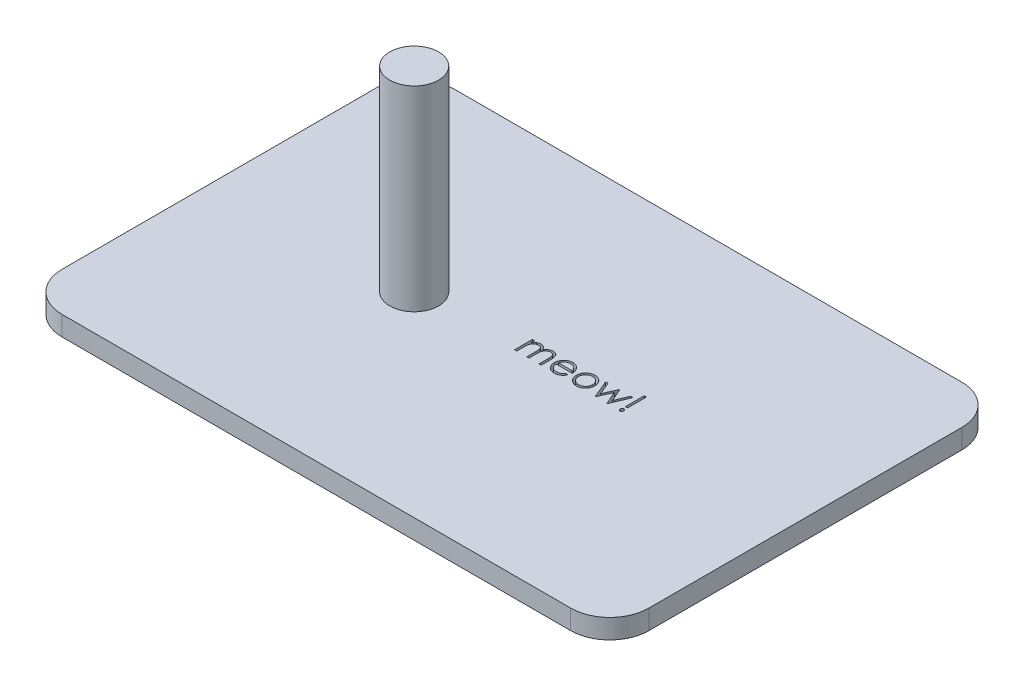
SolidWorks part; units mm, degrees
ref_plane "Front Plane" through (0, 0, 0) normal (0, 0, 1) x (1, 0, 0)
ref_plane "Top Plane" through (0, 0, 0) normal (0, 1, 0) x (1, 0, 0)
ref_plane "Right Plane" through (0, 0, 0) normal (1, 0, 0) x (0, 0, -1)
sketch "Sketch2" plane through (0, 0, 0) normal (0, 1, 0) x (1, 0, 0)
  line L1 (38.1, 25.4) -> (-38.1, 25.4)
  line L2 (38.1, 25.4) -> (38.1, -25.4)
  line L3 (38.1, -25.4) -> (-38.1, -25.4)
  line L4 (-38.1, 25.4) -> (-38.1, -25.4)
  line L6 (-38.1, 25.4) -> (38.1, -25.4) construction
  line L7 (-38.1, -25.4) -> (38.1, 25.4) construction
  point P4 (0, 0)
  point P5 (-40.9995, 28.1845)
  point P6 (-38.1, 23.1418)
  dimension "D1" = 76.2
  dimension "D2" = 50.8
extrude "Boss-Extrude1" add sketch "Sketch2" along normal blind 2.54 contours L4 L3 L2 L1
fillet "Fillet1" radius 5.08 4 edges at (38.1, 1.27, -25.4) (38.1, 1.27, 25.4) (-38.1, 1.27, -25.4) (-38.1, 1.27, 25.4)
sketch "Sketch3" plane through (0, 2.54, 0) normal (0, 1, 0) x (1, 0, 0)
  line L0 (-1.397, 0) -> (1.397, 0) construction
  line L1 (-38.1, 20.32) -> (-38.1, -20.32) construction
  circle A0 centre (-12.7, 0) radius 3.175
  point P4 (-16.0544, 0)
  dimension "D2" = 6.35
  dimension "D1" = 25.4
extrude "Boss-Extrude2" add sketch "Sketch3" along normal blind 25.4
sketch "Sketch5" plane through (0, 2.54, 0) normal (0, 1, 0) x (1, 0, 0)
  text T0 "meow!"
extrude "Cut-Extrude1" cut sketch "Sketch5" against normal through all
